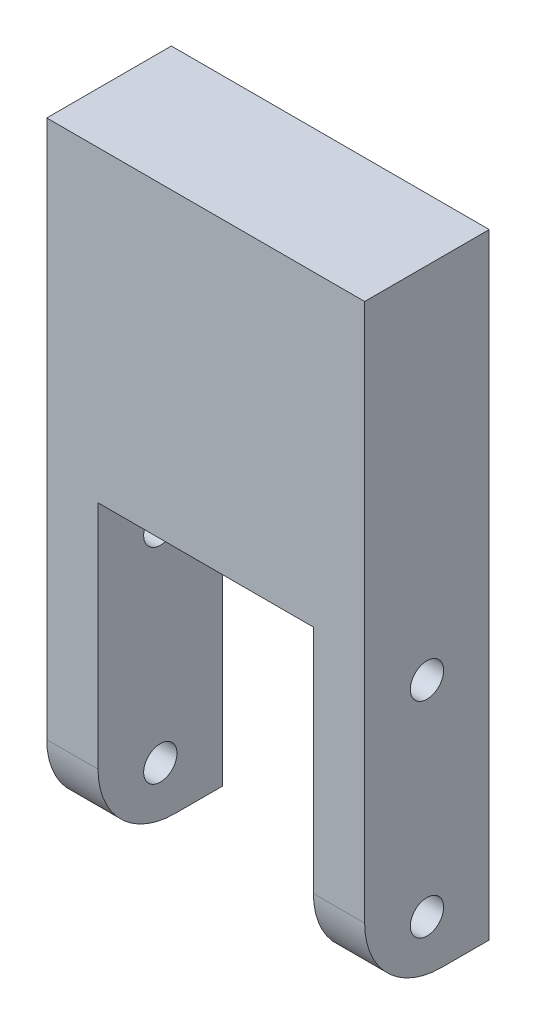
SolidWorks part; units mm, degrees
ref_plane "Front Plane" through (0, 0, 0) normal (0, 0, 1) x (1, 0, 0)
ref_plane "Top Plane" through (0, 0, 0) normal (0, 1, 0) x (1, 0, 0)
ref_plane "Right Plane" through (0, 0, 0) normal (1, 0, 0) x (0, 0, -1)
sketch "Sketch2" plane through (0, 0, 0) normal (0, 0, 1) x (1, 0, 0)
  line L0 (-31, 0) -> (31, 0)
  line L1 (31, 0) -> (31, -120)
  line L2 (31, -120) -> (21, -120)
  line L3 (21, -120) -> (21, -60)
  line L4 (21, -60) -> (-21, -60)
  line L5 (-21, -60) -> (-21, -120)
  line L6 (-21, -120) -> (-31, -120)
  line L7 (-31, -120) -> (-31, 0)
  dimension "D1" = 10
  dimension "D2" = 42
  dimension "D3" = 60
  dimension "D4" = 60
extrude "Boss-Extrude1" add sketch "Sketch2" along normal mid plane 24.3 contours L7 L0 L1 L2 L3 L4 L5 L6
sketch "Sketch3" plane through (0, 0, 0) normal (1, 0, 0) x (0, 0, -1)
  line L0 (-12.15, -120) -> (12.15, -120) construction
  circle A0 centre (0, -70) radius 3.25
  circle A1 centre (0, -110) radius 3.25
  dimension "D1" = 40
  dimension "D3" = 6.5
  dimension "D2" = 10
extrude "Cut-Extrude1" cut sketch "Sketch3" against normal through all both and the other way through all
fillet "Fillet1" radius 15 2 edges at (26, -120, 12.15) (-26, -120, 12.15)
